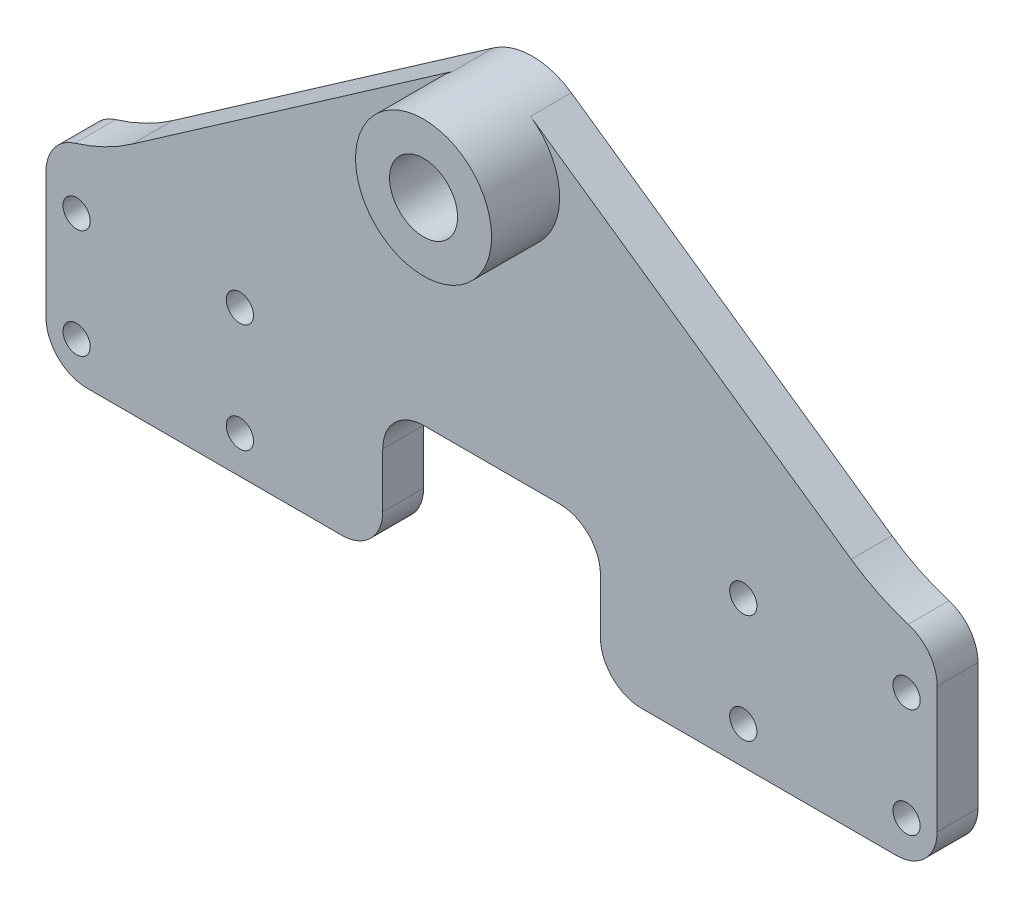
SolidWorks part; units mm, degrees
material "6061-T4 (SS)"
ref_plane "前视基准面" through (0, 0, 0) normal (0, 0, 1) x (1, 0, 0)
ref_plane "上视基准面" through (0, 0, 0) normal (0, 1, 0) x (1, 0, 0)
ref_plane "右视基准面" through (0, 0, 0) normal (1, 0, 0) x (0, 0, -1)
sketch "草图1" plane through (0, 0, 0) normal (0, 0, 1) x (1, 0, 0)
  line L0 (-54.2829, 0) -> (48.6731, 0) construction
  line L1 (0, 54.6129) -> (0, -44.5483) construction
  line L2 (-24.5, 13.8851) -> (-24.5, -36.3545) construction
  line L3 (24.5, 13.8851) -> (24.5, -60.8472) construction
  line L4 (-33, -35) -> (-33, -48.5)
  line L5 (-33, -35) -> (-16, -35)
  line L6 (-16, -35) -> (-16, -48.5)
  line L7 (-33, -48.5) -> (-16, -48.5)
  line L8 (33, -48.5) -> (16, -48.5)
  line L9 (33, -35) -> (33, -48.5)
  line L10 (33, -35) -> (16, -35)
  line L11 (16, -35) -> (16, -48.5)
  line L12 (-37, -35) -> (-12, -35)
  line L13 (-12, -35) -> (-12, -48.5)
  line L14 (-37, -31) -> (-37, -52.5) construction
  line L15 (-37, -35) -> (-37, -48.5)
  line L16 (37, -48.5) -> (12, -48.5)
  line L17 (12, -35) -> (12, -48.5)
  line L18 (37, -35) -> (12, -35)
  line L19 (37, -35) -> (37, -48.5)
  line L20 (-37, -31) -> (-12, -31) construction
  line L21 (-37, -52.5) -> (-12, -52.5) construction
  line L22 (-12, -31) -> (-12, -52.5) construction
  line L23 (-37, -48.5) -> (-12, -48.5)
  dimension "D1" = 24.5
  dimension "D2" = 24.5
  dimension "D3" = 17
  dimension "D4" = 8.5
  dimension "D5" = 13.5
  dimension "D6" = 35
  dimension "D7" = 4
extrude "凸台-拉伸1" add sketch "草图1" along normal blind 3 contours L15 L23 L4 L12 | L6 L23 L13 L12 | L11 L18 L17 L16 | L19 L18 L9 L16 region at (-35, -41.75, 0) region at (-14, -41.75, 0) region at (35, -41.75, 0) region at (14, -41.75, 0)
sketch "草图2" plane through (0, 0, 3) normal (0, 0, 1) x (1, 0, 0)
  line L0 (-37, -48.5) -> (-12, -48.5)
  line L1 (0, 20.7396) -> (0, -60.488) construction
  line L2 (-43.6149, -19) -> (37.5, -19) construction
  line L3 (-37, -35) -> (-37, -48.5)
  line L4 (37, -35) -> (37, -34)
  line L5 (-37, -34) -> (-35, -34)
  line L6 (12, -48.5) -> (37, -48.5)
  line L7 (37, -48.5) -> (37, -35)
  line L8 (37, -34) -> (35, -34)
  line L9 (-2.8571, -14.8967) -> (-26.4286, -31.3098)
  line L10 (2.8571, -14.8967) -> (26.4286, -31.3098)
  line L11 (-8, -48.5) -> (-8, -38.5)
  line L12 (-10, -38.5) -> (10, -38.5) construction
  line L13 (-12, -48.5) -> (12, -48.5)
  line L14 (-37, -35) -> (-37, -34)
  line L15 (-8, -38.5) -> (8, -38.5)
  line L16 (8, -48.5) -> (8, -38.5)
  circle A0 centre (0, -19) radius 2.5
  arc A1 (2.8571, -14.8967) -> (-2.8571, -14.8967) centre (0, -19) ccw
  arc A2 (-35, -34) -> (-26.4286, -31.3098) centre (-35, -19) ccw
  arc A3 (35, -34) -> (26.4286, -31.3098) centre (35, -19) cw
  point P34 (0, -38.5)
  line M9 (-16, -35) -> (-16, -48.5)
  line M10 (-16, -48.5) -> (-12, -48.5)
  line M11 (-12, -48.5) -> (-12, -35)
  line M12 (-12, -35) -> (-16, -35)
  dimension "D2" = 5
  dimension "D4" = 10
  dimension "D1" = 15
  dimension "D6" = 8
  dimension "D3" = 1
  dimension "D5" = 35
  dimension "D7" = 10
  dimension "D9" = 10
extrude "凸台-拉伸2" add sketch "草图2" along normal blind 3 contours L14 L3 L0 L13 L6 L7 M9 M12 M11 | M12 M9 M10 M11 region at (0.5106, -35.1382, 3) region at (-14, -41.75, 3)
fillet "圆角3" radius 3 6 edges at (-37, -48.5, 3) (8, -38.5, 4.5) (-8, -38.5, 4.5) (-8, -48.5, 4.5) (8, -48.5, 4.5) (37, -48.5, 3)
sketch "草图5" plane through (0, 0, 6) normal (0, 0, 1) x (1, 0, 0)
  line L0 (-33, -48.5) -> (-16, -48.5) construction
  line L1 (-33, -48.5) -> (-16, -48.5) construction
  line L2 (-24.5, -53.6012) -> (-24.5, -19) construction
  line L3 (-43.0054, -41.75) -> (-10.7568, -41.75) construction
  line L4 (0, 14.0174) -> (0, -56.268) construction
  circle A0 centre (-18.5, -45.75) radius 1
  circle A1 centre (-18.5, -37.75) radius 1
  circle A2 centre (-30.5, -45.75) radius 1
  circle A3 centre (-30.5, -37.75) radius 1
  circle A4 centre (18.5, -45.75) radius 1
  circle A5 centre (18.5, -37.75) radius 1
  circle A6 centre (30.5, -45.75) radius 1
  circle A7 centre (30.5, -37.75) radius 1
  dimension "D3" = 2
  dimension "D1" = 8.5
  dimension "D2" = 6.75
  dimension "D4" = 4
  dimension "D5" = 6
fillet "圆角4" radius 5 2 edges at (37, -34, 4.5) (-37, -34, 4.5)
chamfer "倒角1" distance 0.5 angle 45 4 edges at (33, -41.75, 0) (16, -41.75, 0) (-16, -41.75, 0) (-33, -41.75, 0)
extrude "切除-拉伸3" cut sketch "草图5" against normal blind 4
sketch "草图9" plane through (0, 0, 6) normal (0, 0, 1) x (1, 0, 0)
  line L1 (37, -45.5) -> (37, -38.7737)
  line L3 (37, -45.5) -> (37, -38.7737)
  line L7 (32.75, -48.5) -> (34, -48.5)
  line L8 (0, -8.0159) -> (0, -56.8084) construction
  line L9 (32.75, -33.8303) -> (32.75, -48.5)
  line L10 (-32.75, -33.8303) -> (-32.75, -48.5)
  line L11 (-32.75, -48.5) -> (-34, -48.5)
  line L12 (-37, -45.5) -> (-37, -38.7737)
  arc A4 (37, -38.7737) -> (32.75, -33.8303) centre (32, -38.7737) ccw
  arc A5 (37, -38.7737) -> (32.75, -33.8303) centre (32, -38.7737) ccw
  arc A6 (34, -48.5) -> (37, -45.5) centre (34, -45.5) ccw
  arc A7 (34, -48.5) -> (37, -45.5) centre (34, -45.5) ccw
  arc A8 (-34, -48.5) -> (-37, -45.5) centre (-34, -45.5) cw
  arc A9 (-37, -38.7737) -> (-32.75, -33.8303) centre (-32, -38.7737) cw
extrude "切除-拉伸4" cut sketch "草图9" against normal blind 14
fillet "圆角6" radius 3 4 edges at (32.75, -48.5, 4.5) (-32.75, -48.5, 4.5) (32.75, -33.8303, 4.5) (-32.75, -33.8303, 4.5)
sketch "草图10" plane through (0, 0, 6) normal (0, 0, 1) x (1, 0, 0)
  circle A0 centre (0, -19) radius 2.5 construction
  circle A1 centre (0, -19) radius 2.5
  arc A2 (2.8571, -14.8967) -> (-2.8571, -14.8967) centre (0, -19) ccw construction
  arc A3 (2.8571, -14.8967) -> (-2.8571, -14.8967) centre (0, -19) ccw
  circle A4 centre (0, -19) radius 5
  arc M5 (2.8571, -14.8967) -> (-2.8571, -14.8967) centre (0, -19) ccw
  circle M21 centre (0, -19) radius 2.5
extrude "凸台-拉伸5" add sketch "草图10" along normal blind 5 contours A4 M5 M21 region at (4.3067, -16.7509, 6)
